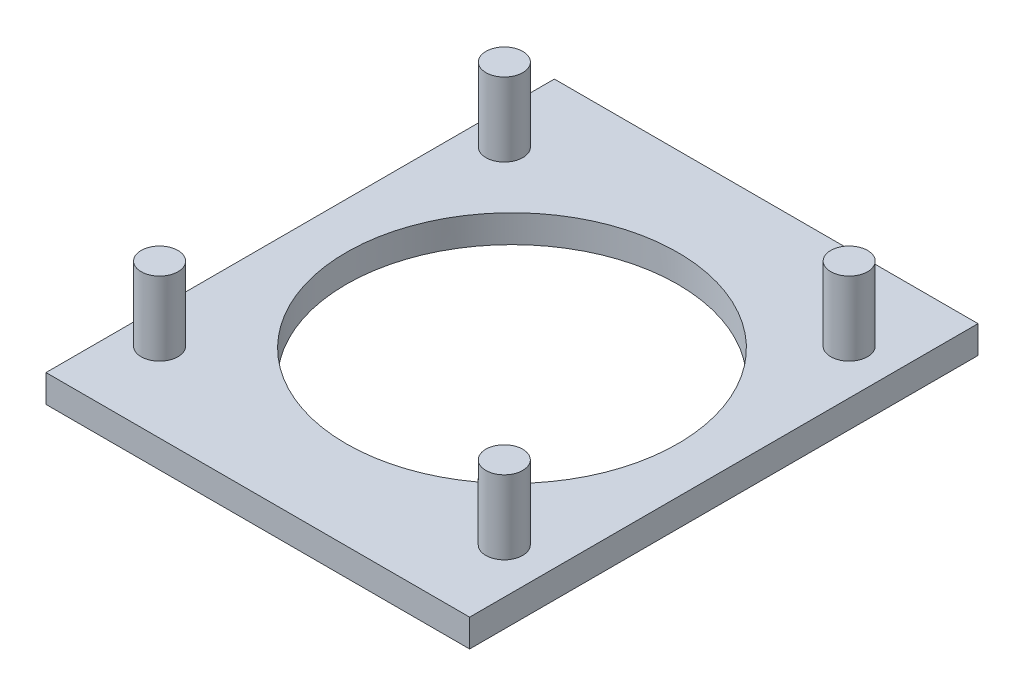
SolidWorks part; units mm, degrees
ref_plane "Front Plane" through (0, 0, 0) normal (0, 0, 1) x (1, 0, 0)
ref_plane "Top Plane" through (0, 0, 0) normal (0, 1, 0) x (1, 0, 0)
ref_plane "Right Plane" through (0, 0, 0) normal (1, 0, 0) x (0, 0, -1)
sketch "Sketch1" plane through (0, 0, 0) normal (0, 1, 0) x (1, 0, 0)
  line L1 (-23, -27.6) -> (23, -27.6)
  line L2 (-23, -27.6) -> (-23, 27.6)
  line L3 (-23, 27.6) -> (23, 27.6)
  line L4 (23, -27.6) -> (23, 27.6)
  line L5 (-23, -27.6) -> (23, 27.6) construction
  line L6 (-23, 27.6) -> (23, -27.6) construction
  point P0 (0, 0)
extrude "Boss-Extrude1" add sketch "Sketch1" along normal blind 3
sketch "Sketch2" plane through (0, 3, 0) normal (0, 1, 0) x (1, 0, 0)
  line L0 (-19.3179, 18.49) -> (18.1221, 18.49)
  line L1 (-19.3179, 18.49) -> (-19.3179, -18.95)
  line L2 (-19.3179, -18.95) -> (18.1221, -18.95)
  line L3 (18.1221, 18.49) -> (18.1221, -18.95)
  circle A0 centre (-19.3179, 18.49) radius 1.25
  circle A1 centre (18.1221, 18.49) radius 1.25
  circle A2 centre (-19.3179, -18.95) radius 1.25
  circle A3 centre (18.1221, -18.95) radius 1.25
sketch "Sketch3" plane through (0, 3, 0) normal (0, 1, 0) x (1, 0, 0)
  circle A0 centre (0, 0) radius 18
sketch "Sketch4" plane through (0, 3, 0) normal (0, 1, 0) x (1, 0, 0)
  line L1 (-16.7358, 33.9203) -> (16.2875, 33.9203)
  line L2 (-16.7358, 33.9203) -> (-16.7358, 13.0921)
  line L3 (-16.7358, 13.0921) -> (16.2875, 13.0921)
  line L4 (16.2875, 33.9203) -> (16.2875, 13.0921)
  line L5 (-16.7358, 33.9203) -> (16.2875, 13.0921) construction
  line L6 (-16.7358, 13.0921) -> (16.2875, 33.9203) construction
  point P0 (-0.2241, 23.5062)
extrude "Cut-Extrude1" [suppressed] cut sketch "Sketch4" against normal blind 8 contours L2 L1 L4 L3
sketch "Sketch5" plane through (0, 3, 0) normal (0, 1, 0) x (1, 0, 0)
  circle A0 centre (-19.3179, 18.49) radius 2
  circle A1 centre (18.1221, 18.49) radius 2
  circle A2 centre (-19.3179, -18.95) radius 2
  circle A3 centre (18.0841, -18.9245) radius 2
extrude "Cut-Extrude2" cut sketch "Sketch3" against normal blind 8
extrude "Boss-Extrude2" add sketch "Sketch5" along normal blind 8
